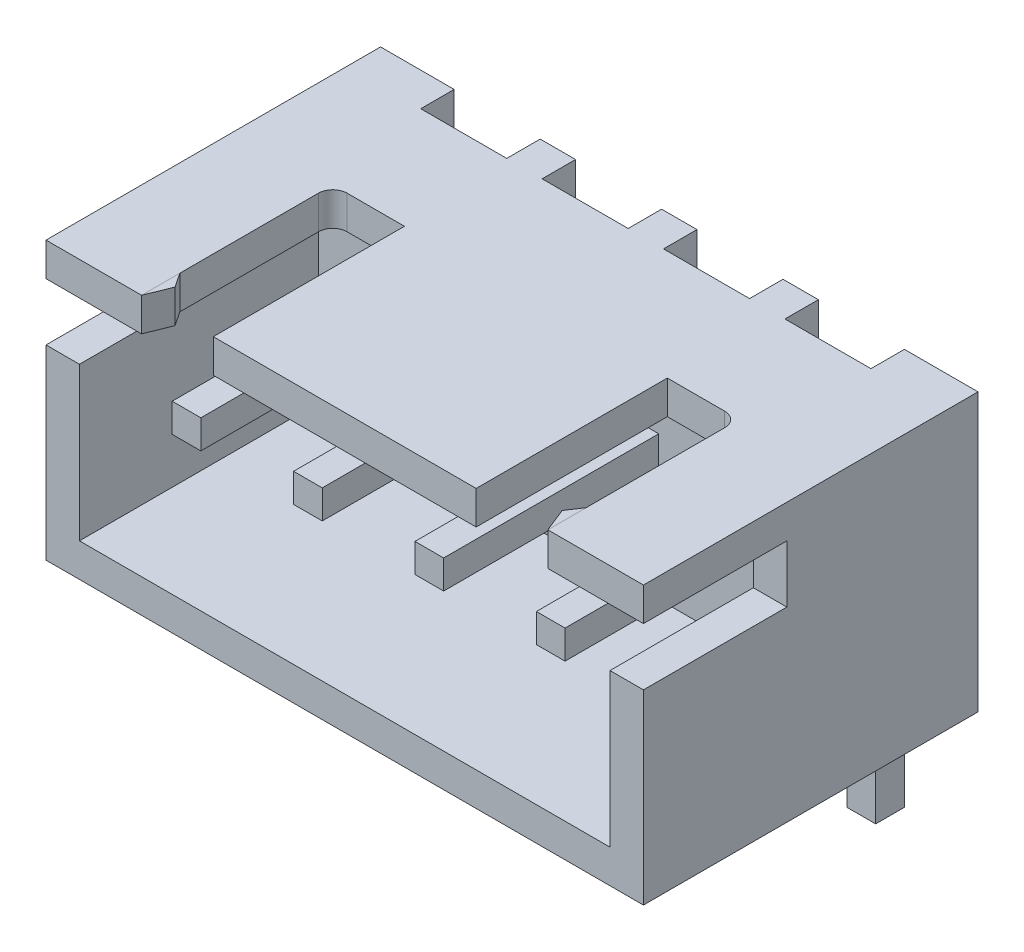
SolidWorks part; units mm, degrees
ref_plane "前视基准面" through (0, 0, 0) normal (0, 0, 1) x (1, 0, 0)
ref_plane "上视基准面" through (0, 0, 0) normal (0, 1, 0) x (1, 0, 0)
ref_plane "右视基准面" through (0, 0, 0) normal (1, 0, 0) x (0, 0, -1)
sketch "草图1" plane through (0, 0, 0) normal (0, 0, 1) x (1, 0, 0)
  line L1 (-6.25, -2.9) -> (6.25, -2.9)
  line L2 (-6.25, -2.9) -> (-6.25, 2.9)
  line L3 (-6.25, 2.9) -> (6.25, 2.9)
  line L4 (6.25, -2.9) -> (6.25, 2.9)
  line L5 (-6.25, -2.9) -> (6.25, 2.9) construction
  line L6 (-6.25, 2.9) -> (6.25, -2.9) construction
  point P0 (0, 0)
  dimension "D1" = 12.5
  dimension "D2" = 5.8
extrude "凸台-拉伸1" add sketch "草图1" along normal blind 7
sketch "草图2" plane through (0, 0, 7) normal (0, 0, 1) x (1, 0, 0)
  line L0 (6.25, -2.9) -> (6.25, 2.9) construction
  line L1 (-5.55, -2.2) -> (5.55, -2.2)
  line L2 (-5.55, -2.2) -> (-5.55, 2.2)
  line L3 (-5.55, 2.2) -> (5.55, 2.2)
  line L4 (5.55, -2.2) -> (5.55, 2.2)
  line L5 (-5.55, -2.2) -> (5.55, 2.2) construction
  line L6 (-5.55, 2.2) -> (5.55, -2.2) construction
  line L7 (-6.25, -2.9) -> (6.25, -2.9) construction
  point P0 (0, 0)
  dimension "D1" = 0.7
  dimension "D2" = 0.7
extrude "切除-拉伸1" cut sketch "草图2" against normal blind 5
sketch "草图3" plane through (0, 0, 7) normal (0, 0, 1) x (1, 0, 0)
  line L0 (-6.25, 2.9) -> (-6.25, -2.9) construction
  line L1 (-5.55, 2.2) -> (-6.25, 2.2)
  line L2 (-5.55, 2.2) -> (-5.55, 1)
  line L3 (-5.55, 1) -> (-6.25, 1)
  line L4 (-6.25, 2.2) -> (-6.25, 1)
  line L5 (0, 4.0159) -> (0, -4.3712) construction
  line L6 (6.25, 2.2) -> (6.25, 1)
  line L7 (5.55, 1) -> (6.25, 1)
  line L8 (5.55, 2.2) -> (5.55, 1)
  line L9 (5.55, 2.2) -> (6.25, 2.2)
  dimension "D1" = 1.2
extrude "切除-拉伸2" cut sketch "草图3" against normal blind 3
sketch "草图4" plane through (0, 0, 7) normal (0, 0, 1) x (1, 0, 0)
  line L0 (6.25, 2.9) -> (-6.25, 2.9) construction
  line L1 (6.25, 2.2) -> (-6.25, 2.2) construction
  line L2 (-4.25, 2.9) -> (-2.75, 2.9)
  line L3 (-4.25, 2.9) -> (-4.25, 2.2)
  line L4 (-4.25, 2.2) -> (-2.75, 2.2)
  line L5 (-2.75, 2.9) -> (-2.75, 2.2)
  line L6 (-6.25, 2.9) -> (-6.25, 2.2) construction
  line L7 (0, 3.8764) -> (0, -3.3054) construction
  line L8 (2.75, 2.9) -> (2.75, 2.2)
  line L9 (4.25, 2.2) -> (2.75, 2.2)
  line L10 (4.25, 2.9) -> (4.25, 2.2)
  line L11 (4.25, 2.9) -> (2.75, 2.9)
  dimension "D1" = 2
  dimension "D2" = 1.5
extrude "切除-拉伸3" cut sketch "草图4" against normal blind 4
fillet "圆角1" radius 0.3 2 edges at (4.25, 2.55, 3) (-4.25, 2.55, 3)
sketch "草图5" plane through (0, 2.9, 0) normal (0, 1, 0) x (1, 0, 0)
  line L0 (-4.25, -7) -> (-4.25, -6.2)
  line L1 (-4.25, -3.3) -> (-4.25, -7) construction
  line L2 (-4.25, -6.2) -> (-4.05, -6.5)
  line L3 (-4.05, -6.5) -> (-4.25, -7)
  line L4 (-5.55, -7) -> (5.55, -7) construction
  line L5 (0, 0.9803) -> (0, -7.8754) construction
  line L6 (4.05, -6.5) -> (4.25, -7)
  line L7 (4.25, -6.2) -> (4.05, -6.5)
  line L8 (4.25, -7) -> (4.25, -6.2)
  dimension "D1" = 0.8
  dimension "D2" = 0.5
  dimension "D3" = 0.2
extrude "凸台-拉伸2" add sketch "草图5" against normal blind 0.7 separate body
sketch "草图6" plane through (0, 0, 2) normal (0, 0, 1) x (1, 0, 0)
  line L0 (-7.6132, 0.5) -> (7.2959, 0.5) construction
  line L1 (-6.25, -2.9) -> (6.25, -2.9) construction
  line L2 (0, 3.6987) -> (0, -3.7749) construction
  line L3 (-4.11, 0.2) -> (-3.51, 0.2)
  line L4 (-4.11, 0.2) -> (-4.11, 0.8)
  line L5 (-4.11, 0.8) -> (-3.51, 0.8)
  line L6 (-3.51, 0.2) -> (-3.51, 0.8)
  line L7 (-4.11, 0.2) -> (-3.51, 0.8) construction
  line L8 (-4.11, 0.8) -> (-3.51, 0.2) construction
  line L9 (-1.57, 0.2) -> (-0.97, 0.2)
  line L10 (-1.57, 0.2) -> (-1.57, 0.8)
  line L11 (-1.57, 0.8) -> (-0.97, 0.8)
  line L12 (-0.97, 0.2) -> (-0.97, 0.8)
  line L13 (-1.57, 0.2) -> (-0.97, 0.8) construction
  line L14 (-1.57, 0.8) -> (-0.97, 0.2) construction
  line L15 (1.57, 0.8) -> (0.97, 0.2) construction
  line L16 (1.57, 0.2) -> (0.97, 0.8) construction
  line L17 (4.11, 0.8) -> (3.51, 0.2) construction
  line L18 (4.11, 0.2) -> (3.51, 0.8) construction
  line L19 (0.97, 0.2) -> (0.97, 0.8)
  line L20 (1.57, 0.8) -> (0.97, 0.8)
  line L21 (1.57, 0.2) -> (1.57, 0.8)
  line L22 (1.57, 0.2) -> (0.97, 0.2)
  line L23 (3.51, 0.2) -> (3.51, 0.8)
  line L24 (4.11, 0.8) -> (3.51, 0.8)
  line L25 (4.11, 0.2) -> (4.11, 0.8)
  line L26 (4.11, 0.2) -> (3.51, 0.2)
  point P4 (-3.81, 0.5)
  point P9 (-1.27, 0.5)
  point P25 (1.27, 0.5)
  point P26 (3.81, 0.5)
  dimension "D1" = 3.4
  dimension "D2" = 0.6
  dimension "D3" = 0.6
  dimension "D4" = 0.6
  dimension "D5" = 0.6
  dimension "D6" = 1.27
  dimension "D7" = 2.54
extrude "凸台-拉伸3" add sketch "草图6" along normal blind 4.5
sketch "草图7" plane through (0, 0, 0) normal (0, 0, -1) x (-1, 0, 0)
  line L0 (-6.25, 2.9) -> (6.25, 2.9) construction
  line L1 (-4.71, 2.9) -> (-2.91, 2.9)
  line L2 (-4.71, 2.9) -> (-4.71, -2.9)
  line L3 (-4.71, -2.9) -> (-2.91, -2.9)
  line L4 (-2.91, 2.9) -> (-2.91, -2.9)
  line L5 (6.25, -2.9) -> (-6.25, -2.9) construction
  line L6 (0, 3.6226) -> (0, -4.7899) construction
  line L7 (-2.17, 2.9) -> (-0.37, 2.9)
  line L8 (-2.17, 2.9) -> (-2.17, -2.9)
  line L9 (-2.17, -2.9) -> (-0.37, -2.9)
  line L10 (-0.37, 2.9) -> (-0.37, -2.9)
  line L11 (0.37, 2.9) -> (0.37, -2.9)
  line L12 (2.17, -2.9) -> (0.37, -2.9)
  line L13 (2.17, 2.9) -> (2.17, -2.9)
  line L14 (2.17, 2.9) -> (0.37, 2.9)
  line L15 (2.91, 2.9) -> (2.91, -2.9)
  line L16 (4.71, -2.9) -> (2.91, -2.9)
  line L17 (4.71, 2.9) -> (4.71, -2.9)
  line L18 (4.71, 2.9) -> (2.91, 2.9)
  dimension "D1" = 1.8
  dimension "D2" = 1.8
  dimension "D3" = 0.37
  dimension "D4" = 2.54
extrude "切除-拉伸4" cut sketch "草图7" against normal blind 0.2
sketch "草图8" plane through (0, 0, 0.2) normal (0, 0, -1) x (-1, 0, 0)
  line L0 (-7.1437, 0.5) -> (7.1056, 0.5) construction
  line L1 (-2.17, -2.9) -> (-0.37, -2.9) construction
  line L2 (0, 3.7749) -> (0, -3.6987) construction
  line L3 (-4.1089, 0.2) -> (-3.5089, 0.2)
  line L4 (-4.1089, 0.2) -> (-4.1089, 0.8)
  line L5 (-4.1089, 0.8) -> (-3.5089, 0.8)
  line L6 (-3.5089, 0.2) -> (-3.5089, 0.8)
  line L7 (-4.1089, 0.2) -> (-3.5089, 0.8) construction
  line L8 (-4.1089, 0.8) -> (-3.5089, 0.2) construction
  line L9 (-1.5689, 0.2) -> (-0.9689, 0.2)
  line L10 (-1.5689, 0.2) -> (-1.5689, 0.8)
  line L11 (-1.5689, 0.8) -> (-0.9689, 0.8)
  line L12 (-0.9689, 0.2) -> (-0.9689, 0.8)
  line L13 (-1.5689, 0.2) -> (-0.9689, 0.8) construction
  line L14 (-1.5689, 0.8) -> (-0.9689, 0.2) construction
  line L15 (1.5689, 0.8) -> (0.9689, 0.2) construction
  line L16 (1.5689, 0.2) -> (0.9689, 0.8) construction
  line L17 (4.1089, 0.8) -> (3.5089, 0.2) construction
  line L18 (4.1089, 0.2) -> (3.5089, 0.8) construction
  line L19 (0.9689, 0.2) -> (0.9689, 0.8)
  line L20 (1.5689, 0.8) -> (0.9689, 0.8)
  line L21 (1.5689, 0.2) -> (1.5689, 0.8)
  line L22 (1.5689, 0.2) -> (0.9689, 0.2)
  line L23 (3.5089, 0.2) -> (3.5089, 0.8)
  line L24 (4.1089, 0.8) -> (3.5089, 0.8)
  line L25 (4.1089, 0.2) -> (4.1089, 0.8)
  line L26 (4.1089, 0.2) -> (3.5089, 0.2)
  point P4 (-3.8089, 0.5)
  point P9 (-1.2689, 0.5)
  point P25 (1.2689, 0.5)
  point P26 (3.8089, 0.5)
  dimension "D1" = 3.4
  dimension "D2" = 0.6
  dimension "D3" = 0.6
  dimension "D4" = 0.6
  dimension "D5" = 0.6
  dimension "D6" = 1.2689
  dimension "D7" = 2.54
extrude "凸台-拉伸4" add sketch "草图8" along normal blind 0.2
sketch "草图9" plane through (0, 0, 0) normal (0, 0, -1) x (-1, 0, 0)
  line L1 (-4.1089, 0.8) -> (-3.5089, 0.8)
  line L2 (-4.1089, 0.8) -> (-4.1089, -6)
  line L3 (-4.1089, -6) -> (-3.5089, -6)
  line L4 (-3.5089, 0.8) -> (-3.5089, -6)
  line L5 (-1.5689, 0.8) -> (-0.9689, 0.8)
  line L6 (-1.5689, 0.8) -> (-1.5689, -6)
  line L7 (-1.5689, -6) -> (-0.9689, -6)
  line L8 (-0.9689, 0.8) -> (-0.9689, -6)
  line L9 (0, 4.1653) -> (0, -3.8892) construction
  line L10 (0.9689, 0.8) -> (0.9689, -6)
  line L11 (1.5689, -6) -> (0.9689, -6)
  line L12 (1.5689, 0.8) -> (1.5689, -6)
  line L13 (1.5689, 0.8) -> (0.9689, 0.8)
  line L14 (3.5089, 0.8) -> (3.5089, -6)
  line L15 (4.1089, -6) -> (3.5089, -6)
  line L16 (4.1089, 0.8) -> (4.1089, -6)
  line L17 (4.1089, 0.8) -> (3.5089, 0.8)
  dimension "D1" = 0.6
  dimension "D2" = 6.8
  dimension "D3" = 0.6
  dimension "D4" = 6.8
extrude "凸台-拉伸5" add sketch "草图9" along normal blind 0.6
fillet "圆角2" radius 0.3 4 edges at (-3.8089, 0.8, -0.6) (-1.2689, 0.8, -0.6) (1.2689, 0.8, -0.6) (3.8089, 0.8, -0.6)
fillet "圆角3" radius 0.2 4 edges
chamfer "倒角1" distance 0.5 distance2 1.5 4 edges at (-3.81, 2.9, 0.2) (-1.27, 2.9, 0.2) (1.27, 2.9, 0.2) (3.81, 2.9, 0.2) first distance on face at (0, 2.9, 2.0692)
chamfer "倒角2" distance 0.5 distance2 2.5 4 edges at (-3.81, -2.9, 0.2) (-1.27, -2.9, 0.2) (1.27, -2.9, 0.2) (3.81, -2.9, 0.2) first distance on face at (0, -2.9, 0.78)
